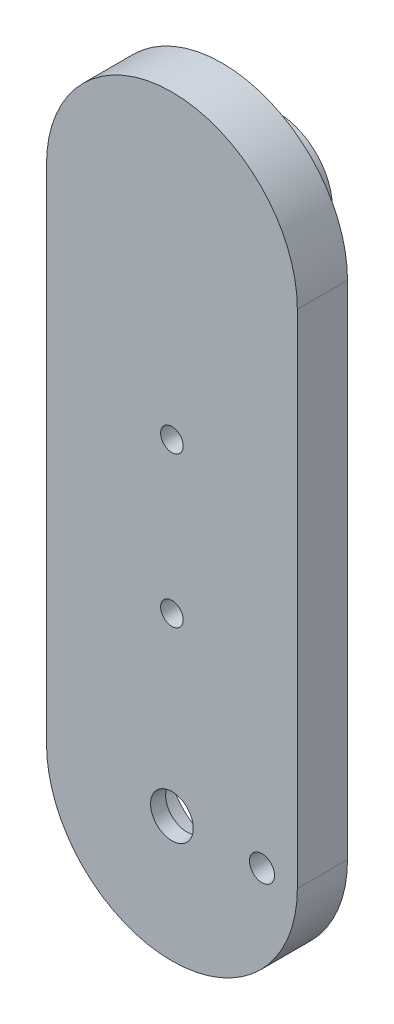
SolidWorks part; units mm, degrees
material "ABS"
ref_plane "Alzado" through (0, 0, 0) normal (0, 0, 1) x (1, 0, 0)
ref_plane "Planta" through (0, 0, 0) normal (0, 1, 0) x (1, 0, 0)
ref_plane "Vista lateral" through (0, 0, 0) normal (1, 0, 0) x (0, 0, -1)
sketch "Croquis1" plane through (0, 0, 0) normal (0, 0, 1) x (1, 0, 0)
  line L0 (0, 0) -> (0, 2.5) construction
  line L1 (1.833, 2.5) -> (-1.833, 2.5)
  arc A0 (-1.833, 2.5) -> (1.833, 2.5) centre (0, 0) ccw
  circle A1 centre (0, 0) radius 11
  point P8 (0, 2.5)
  dimension "D1" = 6.2
  dimension "D2" = 22
  dimension "D3" = 2.5
extrude "Saliente-Extruir1" add sketch "Croquis1" along normal mid plane 10
sketch "Croquis2" plane through (0, 0, 5) normal (0, 0, 1) x (1, 0, 0)
  circle A1 centre (0, 0) radius 11
  circle A2 centre (0, 0) radius 11
  dimension "D1" = 0
extrude "Saliente-Extruir2" add sketch "Croquis2" along normal blind 6
sketch "Croquis3" plane through (0, 0, 0) normal (0, 1, 0) x (1, 0, 0)
  line L0 (0, 5) -> (0, 0) construction
  line L1 (3.1, 5) -> (-3.1, 5) construction
  circle A0 centre (0, 0) radius 2.25
  dimension "D2" = 4.5
  dimension "D1" = 5
extrude "Cortar-Extruir1" cut sketch "Croquis3" along normal through all
sketch "Croquis4" plane through (0, 0, 11) normal (0, 0, 1) x (1, 0, 0)
  line L0 (-25, 0) -> (-25, -85)
  line L1 (-25, -85) -> (25, -85)
  line L2 (25, -85) -> (25, 0)
  arc A0 (25, 0) -> (-25, 0) centre (0, 0) ccw
  dimension "D1" = 50
  dimension "D2" = 85
extrude "Saliente-Extruir3" add sketch "Croquis4" against normal blind 5 and the other way blind 5
sketch "Croquis5" plane through (0, 0, 16) normal (0, 0, 1) x (1, 0, 0)
  line L0 (0, 0) -> (0, -100) construction
  line L1 (-25, -100) -> (-25, -85)
  line L2 (-25, -85) -> (25, -85)
  line L3 (25, -85) -> (25, -100)
  arc A0 (-25, -100) -> (25, -100) centre (0, -100) ccw
  dimension "D1" = 100
extrude "Saliente-Extruir4" add sketch "Croquis5" against normal up to surface (10 mm away) up to face at (11, 0, 6)
sketch "Croquis6" plane through (0, 0, 16) normal (0, 0, 1) x (1, 0, 0)
  line L0 (-25, -50) -> (25, -50) construction
  line L1 (-25, 0) -> (-25, -100) construction
  line L2 (25, -100) -> (25, 0) construction
  line L3 (0, -65) -> (0, -35) construction
  circle A0 centre (0, -35) radius 2.25
  circle A1 centre (0, -65) radius 2.25
  point P10 (0, -50)
  dimension "D2" = 4.5
  dimension "D1" = 30
extrude "Cortar-Extruir2" cut sketch "Croquis6" against normal through all
sketch "Croquis7" plane through (0, 0, 6) normal (0, 0, -1) x (-1, 0, 0)
  circle A0 centre (0, -100) radius 10.9
  dimension "D1" = 21.8
extrude "Cortar-Extruir3" cut sketch "Croquis7" against normal blind 7
sketch "Croquis8" plane through (0, 0, 13) normal (0, 0, -1) x (-1, 0, 0)
  circle A0 centre (0, -100) radius 4.25
  dimension "D1" = 8.5
extrude "Cortar-Extruir4" cut sketch "Croquis8" against normal through all
sketch "Croquis9" plane through (0, 0, 16) normal (0, 0, 1) x (1, 0, 0)
  line L0 (10.9, -100) -> (17.95, -100) construction
  line L1 (17.95, -100) -> (25, -100) construction
  circle A1 centre (17.95, -100) radius 2.5
  circle A2 centre (0, -100) radius 10.9 construction
  circle A3 centre (0, -100) radius 10.9 construction
  dimension "D1" = 5
extrude "Cortar-Extruir5" cut sketch "Croquis9" against normal through all
